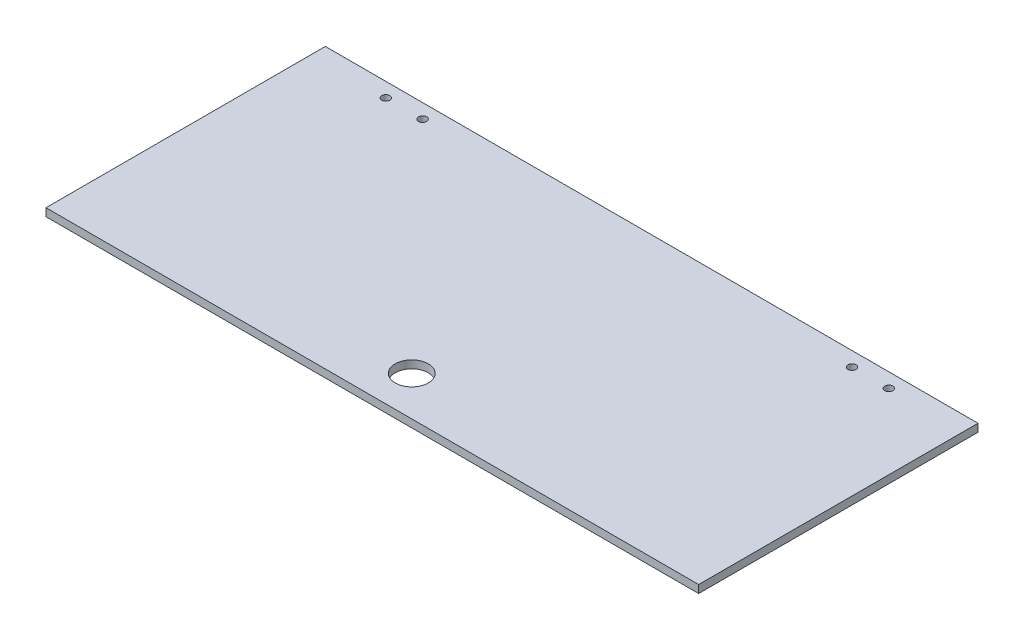
SolidWorks part; units mm, degrees
ref_plane "Front Plane" through (0, 0, 0) normal (0, 0, 1) x (1, 0, 0)
ref_plane "Top Plane" through (0, 0, 0) normal (0, 1, 0) x (1, 0, 0)
ref_plane "Right Plane" through (0, 0, 0) normal (1, 0, 0) x (0, 0, -1)
sketch "Sketch1" plane through (0, 0, 0) normal (0, 1, 0) x (1, 0, 0)
  line L0 (125, 107) -> (125, 0) construction
  line L1 (0, 107) -> (250, 107)
  line L2 (0, 107) -> (0, 0)
  line L3 (0, 0) -> (250, 0)
  line L4 (250, 107) -> (250, 0)
  circle A0 centre (28.65, 101.5) radius 1.55
  circle A1 centre (42.75, 101.5) radius 1.55
  circle A2 centre (207.25, 101.5) radius 1.55
  circle A3 centre (221.35, 101.5) radius 1.55
  circle A4 centre (125, 15.1) radius 6.35
  point P17 (0, 0)
  point P18 (0, 0)
  dimension "D2" = 3.1
  dimension "D7" = 12.7
  dimension "D8" = 15.1
  dimension "D1" = 250
  dimension "D3" = 14.1
  dimension "D4" = 28.65
  dimension "D5" = 5.5
  dimension "D6" = 107
extrude "Boss-Extrude1" add sketch "Sketch1" along normal blind 3
equation "\"cf_tube_outer_diameter\"= 25mm"
equation "\"cf_tube_inner_diameter\" = 21mm"
equation "\"mid_plate_mid_to_top\" = 100mm"
equation "\"mid_plate_mid_to_bottom\" = 30mm"
equation "\"mid_plate_horizontal_spacing\"=250mm"
equation "\"cf_plate_thickness\" =4mm"
equation "\"mid_tube_length\" = 121mm"
equation "\"mid_plate_bottom_width\" = 180mm"
equation "\"mid_support_plate_distance\" = 250mm"
equation "\"nut_strip_2_hole_distance\" = 7mm"
equation "\"nut_strip_hole_diameter\" = 2.5mm"
equation "\"nut_strip_hole_to_edge_distance\"= 2.5mm"
